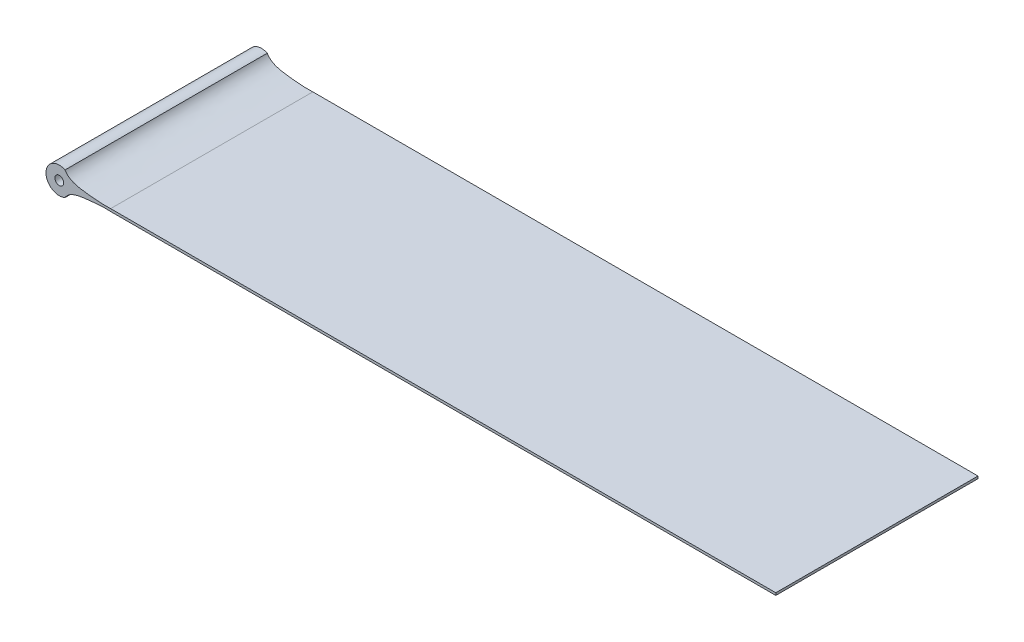
SolidWorks part; units mm, degrees
material "Plastique personnalisé"
ref_plane "Plan de face" through (0, 0, 0) normal (0, 0, 1) x (1, 0, 0)
ref_plane "Plan de dessus" through (0, 0, 0) normal (0, 1, 0) x (1, 0, 0)
ref_plane "Plan de droite" through (0, 0, 0) normal (1, 0, 0) x (0, 0, -1)
sketch "Esquisse2" plane through (0, 0, 0) normal (0, 0, 1) x (1, 0, 0)
  line L0 (5.7911, 0.1421) -> (80.7911, 0.1332)
  line L1 (0, 0) -> (12.6201, 0) construction
  line L2 (5.7911, -0.1421) -> (80.7911, -0.1332)
  arc A0 (0.6509, 1.3514) -> (0.6509, -1.3514) centre (0, 0) ccw
  circle A1 centre (0, 0) radius 0.5
  arc A2 (80.7911, 0.1332) -> (80.7911, -0.1332) centre (20.6774, 0) cw
  spline S0 degree 3 poles (0.6509, 1.3514) (1.1145, 0.5104) (3.0699, 0.2682) (5.0293, 0.0873) (5.7911, 0.1421) knots 0 0 0 0 0.614721 1 1 1 1
  spline S1 degree 3 poles (0.6509, -1.3514) (1.1145, -0.5104) (3.0699, -0.2682) (5.0293, -0.0873) (5.7911, -0.1421) knots 0 0 0 0 0.614721 1 1 1 1
  dimension "D1" = 3
  dimension "D2" = 1
  dimension "D3" = 75
extrude "Boss.-Extru.1" add sketch "Esquisse2" along normal blind 11.4 and the other way blind 11.4
